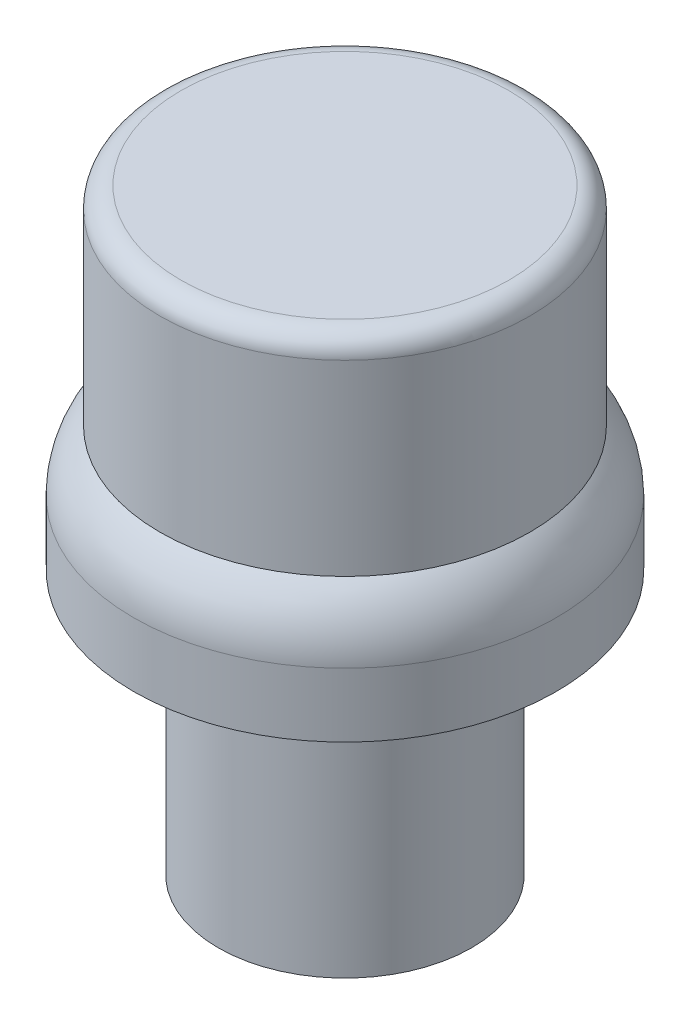
SolidWorks part; units mm, degrees
ref_plane "Front Plane" through (0, 0, 0) normal (0, 0, 1) x (1, 0, 0)
ref_plane "Top Plane" through (0, 0, 0) normal (0, 1, 0) x (1, 0, 0)
ref_plane "Right Plane" through (0, 0, 0) normal (1, 0, 0) x (0, 0, -1)
sketch "Sketch1" plane through (0, 0, 0) normal (0, 1, 0) x (1, 0, 0)
  circle A0 centre (0, 0) radius 5.08
  dimension "D1" = 10.16
extrude "Boss-Extrude1" add sketch "Sketch1" along normal blind 3
sketch "Sketch2" plane through (0, 3, 0) normal (0, 1, 0) x (1, 0, 0)
  circle A0 centre (0, 0) radius 4.445
extrude "Boss-Extrude2" add sketch "Sketch2" along normal blind 5
fillet "Fillet2" radius 2 1 edges at (0, 3, 5.08)
fillet "Fillet3" radius 0.5 1 edges at (0, 8, 4.445)
sketch "Sketch3" plane through (0, 0, 0) normal (0, -1, 0) x (1, 0, 0)
  circle A0 centre (0, 0) radius 3.048
extrude "Boss-Extrude3" add sketch "Sketch3" along normal blind 6.35
sketch "Sketch4" plane through (0, -6.35, 0) normal (0, -1, 0) x (1, 0, 0)
  line L1 (-0.7937, -0.745) -> (0.7937, -0.745)
  line L2 (-0.7937, -0.745) -> (-0.7937, 0.745)
  line L3 (-0.7937, 0.745) -> (0.7937, 0.745)
  line L4 (0.7937, -0.745) -> (0.7937, 0.745)
  line L5 (-0.7937, -0.745) -> (0.7937, 0.745) construction
  line L6 (-0.7937, 0.745) -> (0.7937, -0.745) construction
  point P0 (0, 0)
extrude "Cut-Extrude1" cut sketch "Sketch4" against normal blind 1.27
